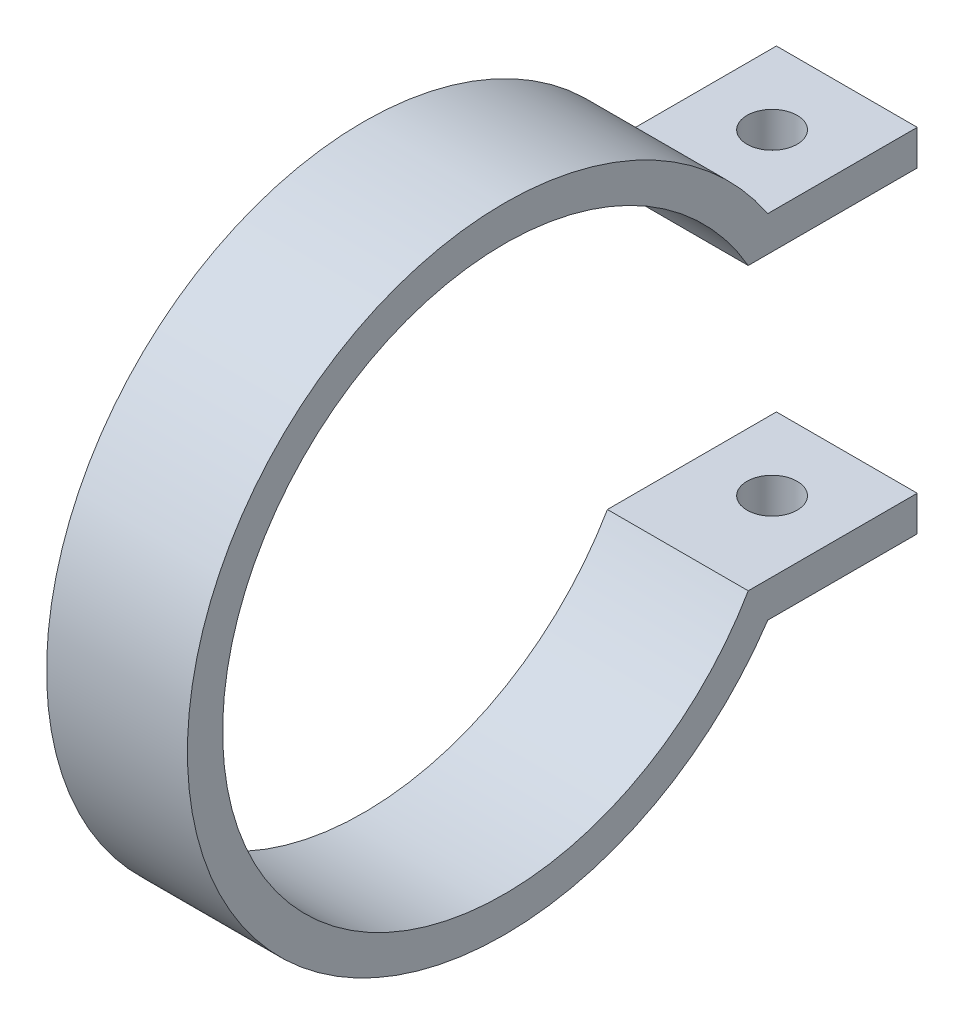
SolidWorks part; units mm, degrees
material "6061-T6 (SS)"
ref_plane "Front Plane" through (0, 0, 0) normal (1, 0, 0) x (0, 1, 0)
ref_plane "Top Plane" through (0, 0, 0) normal (0, 0, 1) x (0, 1, 0)
ref_plane "Right Plane" through (0, 0, 0) normal (0, 1, 0) x (-1, 0, 0)
sketch "Sketch2" plane through (0, 0, 0) normal (1, 0, 0) x (0, 1, 0)
  line L0 (-6.35, -10.9985) -> (6.35, -10.9985) construction
  line L1 (-6.35, -10.9985) -> (-6.35, -18.6185)
  line L2 (6.35, -10.9985) -> (6.35, -18.6185)
  line L3 (-7.9375, -11.8798) -> (-7.9375, -18.6185)
  line L4 (-7.9375, -18.6185) -> (-6.35, -18.6185)
  line L5 (6.35, -18.6185) -> (7.9375, -18.6185)
  line L6 (7.9375, -18.6185) -> (7.9375, -11.8798)
  arc A0 (6.35, -10.9985) -> (-6.35, -10.9985) centre (0, 0) ccw
  arc A1 (7.9375, -11.8798) -> (-7.9375, -11.8798) centre (0, 0) ccw
  dimension "D2" = 12.7
  dimension "D4" = 14.2875
  dimension "D1" = 12.7
  dimension "D3" = 7.62
  dimension "D5" = 1.5875
  dimension "D6" = 1.5875
extrude "Boss-Extrude1" add sketch "Sketch2" along normal blind 6.35
sketch "Sketch3" plane through (0, -7.9375, 0) normal (0, -1, 0) x (1, 0, 0)
  line L0 (0, -11.8798) -> (6.35, -18.6185) construction
  point P9 (3.175, -15.2491)
hole_wizard "Tap Drill for #4-40 Tap1" positions "Sketch3" profile "Sketch4" hole size "#4-40" standard "ANSI Inch" end condition through all
sketch "Sketch4" plane through (3.175, -7.9375, -15.2491) normal (1, 0, 0) x (0, 0, -1)
  line L0 (0, 0) -> (0, 22.225)
  line L1 (0, 22.225) -> (1.1303, 22.225)
  line L2 (1.1303, 22.225) -> (1.1303, 0)
  line L5 (1.1303, 0) -> (0, 0)
  line L11 (0, -6.35) -> (0, 107.95) construction
  dimension "Thru Hole Dia." = 2.2606
  dimension "Thru Hole Depth" = 22.225
